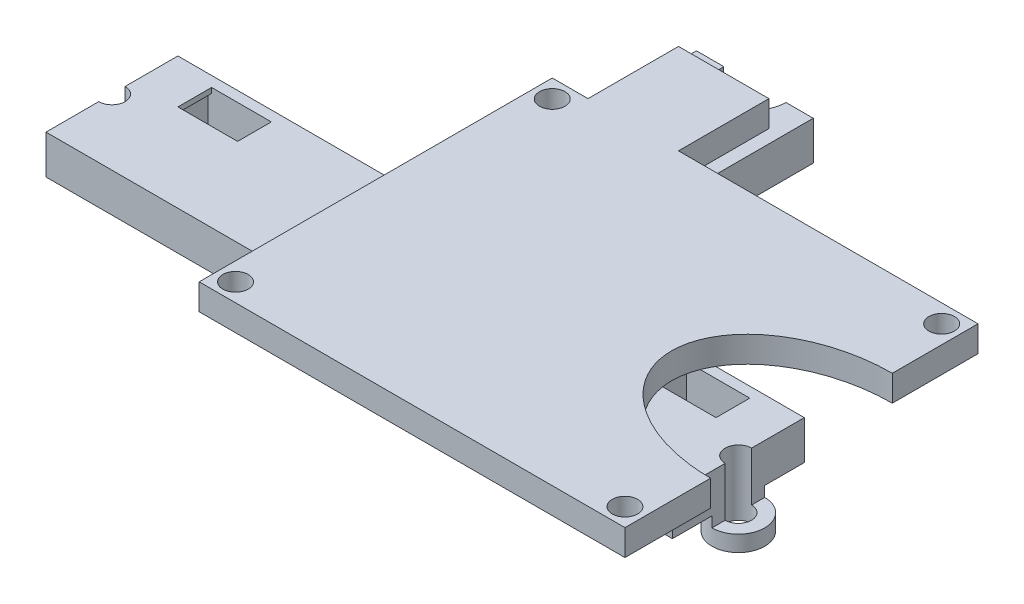
SolidWorks part; units mm, degrees
ref_plane "Front Plane" through (0, 0, 0) normal (0, 0, 1) x (1, 0, 0)
ref_plane "Top Plane" through (0, 0, 0) normal (0, 1, 0) x (1, 0, 0)
ref_plane "Right Plane" through (0, 0, 0) normal (1, 0, 0) x (0, 0, -1)
sketch "Sketch3" plane through (0, 0, 0) normal (0, 1, 0) x (1, 0, 0)
  line L0 (0, -55) -> (0, 55) construction
  line L1 (-60.325, -12.7) -> (60.325, -12.7)
  line L2 (-60.325, -12.7) -> (-60.325, 12.7)
  line L3 (-60.325, 12.7) -> (60.325, 12.7)
  line L4 (60.325, -12.7) -> (60.325, 12.7)
  line L5 (-60.325, -12.7) -> (60.325, 12.7) construction
  line L6 (-60.325, 12.7) -> (60.325, -12.7) construction
  circle A0 centre (-60.325, 0) radius 2.54
  circle A1 centre (-60.325, 0) radius 5.08
  circle A2 centre (60.325, 0) radius 5.08
  circle A3 centre (60.325, 0) radius 2.54
  point P0 (0, 0)
  dimension "D3" = 5.08
  dimension "D1" = 120.65
  dimension "D2" = 25.4
  dimension "D4" = 2.54
extrude "Boss-Extrude1" add sketch "Sketch3" along normal blind 7.5 contours L4 A2 L3 L2 A1 L1 | L2 A1 A0 | L4 A3 A2 region at (0, 0, 0) region at (-60.2114, 0, 3.81) region at (55.3586, 0, 0)
sketch "Sketch4" plane through (0, 7.5, 0) normal (0, 1, 0) x (1, 0, 0)
  line L5 (-15, 6.25) -> (45, 6.25)
  line L6 (-15, 6.25) -> (-15, -6.25)
  line L15 (-15, -6.25) -> (45, -6.25)
  line L16 (45, 6.25) -> (45, -6.25)
  line L18 (-15, 6.25) -> (-15, -6.25)
  line L20 (45, 6.25) -> (45, -6.25)
  point P1 (-15, 0)
  dimension "D1" = 60
  dimension "D2" = 15
  dimension "D5" = 12.5
sketch "Sketch5" plane through (0, 7.5, 0) normal (0, 1, 0) x (1, 0, 0)
  line L0 (-60.325, 12.7) -> (60.325, 12.7) construction
  line L1 (-11.25, 12.7) -> (11.25, 12.7)
  line L2 (-11.25, 12.7) -> (-11.25, 63.5)
  line L3 (-11.25, 63.5) -> (11.25, 63.5)
  line L4 (11.25, 12.7) -> (11.25, 63.5)
  circle A0 centre (0, 63.5) radius 6
  point P6 (0, 63.5)
  line M9 (60.325, 12.7) -> (-60.325, 12.7)
  dimension "D3" = 12
  dimension "D1" = 22.5
  dimension "D2" = 50.8
extrude "Boss-Extrude2" add sketch "Sketch5" against normal blind 7.5 contours A0 L3 L2 L4 M9 region at (0, 7.5, -36.9105)
sketch "Sketch6" plane through (0, 7.5, 0) normal (0, 1, 0) x (1, 0, 0)
  line L0 (-15.6, -27.9202) -> (-15.6, -24.4202) construction
  line L1 (66.4, -27.9202) -> (66.4, 40.0798)
  line L2 (66.4, -27.9202) -> (-15.6, -27.9202)
  line L3 (-15.6, -27.9202) -> (-15.6, 40.0798)
  line L4 (66.4, 40.0798) -> (-15.6, 40.0798)
  line L5 (66.4, -27.9202) -> (-15.6, 40.0798) construction
  line L6 (-15.6, -27.9202) -> (66.4, 40.0798) construction
  line L7 (-15.6, -24.4202) -> (-12.1, -24.4202) construction
  line L8 (-15.6, 6.0798) -> (25.4, 6.0798) construction
  line L9 (25.4, 6.0798) -> (25.4, 50.2397) construction
  circle A0 centre (-12.1, -24.4202) radius 2.45
  circle A1 centre (-12.1, 36.5798) radius 2.45
  circle A2 centre (62.9, 36.5798) radius 2.45
  circle A3 centre (62.9, -24.4202) radius 2.45
  point P0 (25.4, 6.0798)
  line M36 (-11.25, 63.5) -> (-11.25, 12.7)
  dimension "D5" = 4.9
  dimension "D1" = 82
  dimension "D2" = 68
  dimension "D3" = 3.5
  dimension "D4" = 3.5
  dimension "D6" = 3.5
  dimension "D7" = 3.5
  dimension "D8" = 25.4
  dimension "D9" = 6.0798
extrude "Boss-Extrude4" add sketch "Sketch6" along normal blind 5
sketch "Sketch7" plane through (0, 7.5, 0) normal (0, 1, 0) x (1, 0, 0)
  line L0 (66.4, 40.0798) -> (-15.6, 40.0798) construction
  line L6 (-8.7101, 57.5) -> (8.7101, 57.5)
  line L7 (-8.7101, 57.5) -> (-8.7101, 40.0798)
  line L8 (-8.7101, 40.0798) -> (8.7101, 40.0798)
  line L9 (8.7101, 57.5) -> (8.7101, 40.0798)
  arc A0 (-6, 63.5) -> (6, 63.5) centre (0, 63.5) ccw construction
  point P7 (0, 57.5)
extrude "Boss-Extrude5" add sketch "Sketch7" along normal up to surface (5 mm away) up to face at (25.4, 12.5, -6.0798)
extrude "Boss-Extrude6" add sketch "Sketch3<3>" against normal blind 5.08 contours L2 A1 A0 | L2 A1 A0 | L4 A3 A2 | L4 A3 A2 region at (-65.2914, 0, 0) region at (-60.2114, 0, 3.81) region at (55.3586, 0, 0) region at (60.4386, 0, 3.81)
sketch "Sketch3<3>" plane through (0, 0, 0) normal (0, 1, 0) x (1, 0, 0) same geometry as "Sketch3"
extrude "Cut-Extrude1" cut sketch "Sketch3<4>" against normal offset from surface (2 mm away) 9.5 contours L2 A1 A0 region at (-65.2914, 0, 0) up to face at (7.8605, 7.5, -53.4862)
sketch "Sketch3<4>" plane through (0, 0, 0) normal (0, 1, 0) x (1, 0, 0) same geometry as "Sketch3"
mirror "Mirror2" about plane through (0, 0, 0) normal (1, 0, 0) of "Cut-Extrude1"
extrude "Boss-Extrude7" add sketch "Sketch6<3>" along normal blind 1 contours A0 | A1 M36 | A1 M36 | A2 | A3 region at (-10.5878, 7.5, -36.5798) region at (-12.6988, 7.5, -36.5798) region at (-12.1, 7.5, 24.4202) region at (62.9, 7.5, -36.5798) region at (62.9, 7.5, 24.4202)
sketch "Sketch6<3>" plane through (0, 7.5, 0) normal (0, 1, 0) x (1, 0, 0) same geometry as "Sketch6"
sketch "Sketch8" plane through (0, 12.5, 0) normal (0, 1, 0) x (1, 0, 0)
  line L3 (66.4, -27.9202) -> (66.4, 40.0798) construction
  ellipse E0 centre (66.4, 6.0798) end of major axis (41.4, 6.0798) minor radius 17.5
extrude "Cut-Extrude4" cut sketch "Sketch8" against normal up to surface (5 mm away) up to face at (36.286, 7.5, -2.4319)
sketch "Sketch9" plane through (0, 0, -12.7) normal (0, 0, -1) x (-1, 0, 0)
  line L0 (60.325, 7.5) -> (51.825, 7.5)
  line L1 (60.325, 7.5) -> (15.6, 7.5) construction
  line L2 (51.825, 7.5) -> (51.825, 6.5)
  line L3 (51.825, 7.5) -> (40.325, 7.5)
  line L4 (40.325, 7.5) -> (40.325, 6.5)
  line L5 (46.075, 7.5) -> (46.075, 6.5) construction
  line L6 (40.325, 6.5) -> (51.825, 6.5)
  line L7 (40.325, 6.5) -> (40.325, 0)
  line L8 (40.325, 0) -> (51.825, 0)
  line L9 (51.825, 6.5) -> (51.825, 0)
  line L10 (52.525, 6.5) -> (52.525, 0)
  line L11 (60.325, 0) -> (11.25, 0) construction
  line L12 (46.075, 7.5) -> (39.625, 7.5)
  line L13 (40.325, 6.5) -> (39.625, 6.5)
  line L14 (39.625, 6.5) -> (39.625, 0)
  line L15 (51.825, 6.5) -> (52.525, 6.5)
  line L16 (39.625, 0) -> (52.525, 0)
  line M15 (11.25, 0) -> (60.325, 0)
  line M17 (60.325, 7.5) -> (15.6, 7.5)
  dimension "D1" = 8.5
  dimension "D2" = 11.5
  dimension "D3" = 1
  dimension "D4" = 6.45
extrude "Cut-Extrude5" cut sketch "Sketch9" against normal blind 6.5 from offset 2 contours L13 L14 L7 M15 | L9 L6 L7 M15 | L15 L9 L10 M15 | L5 L6 L2 M17 | L5 L3 L4 L6 region at (-48.95, 7, -12.7) region at (-46.075, 3.25, -12.7) region at (-52.175, 3.25, -12.7) region at (-43.2, 7, -12.7) region at (-39.975, 3.25, -12.7) offset against normal yes
mirror "Mirror3" about plane through (0, 0, 0) normal (1, 0, 0) of "Cut-Extrude5"
